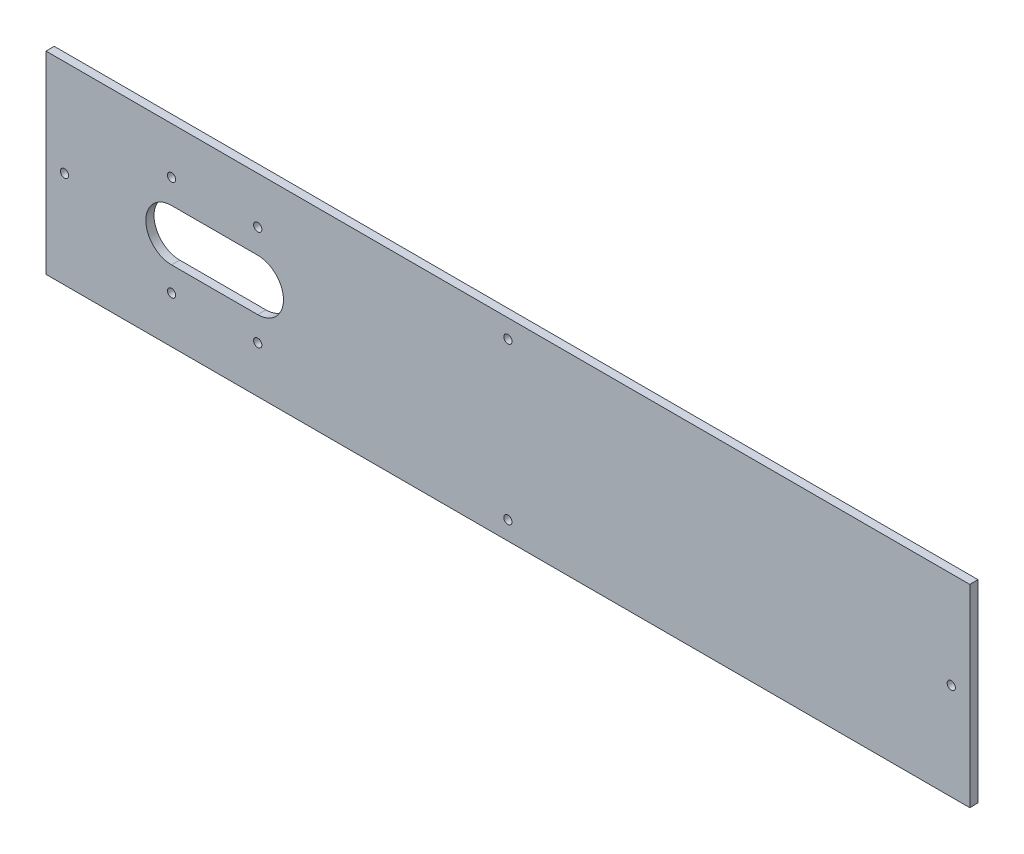
SolidWorks part; units mm, degrees
ref_plane "Piano frontale" through (0, 0, 0) normal (0, 0, 1) x (1, 0, 0)
ref_plane "Piano superiore" through (0, 0, 0) normal (0, 1, 0) x (1, 0, 0)
ref_plane "Piano destro" through (0, 0, 0) normal (1, 0, 0) x (0, 0, -1)
sketch "Schizzo1" plane through (0, 0, 0) normal (0, 0, 1) x (1, 0, 0)
  line L0 (-224.5, 351.6275) -> (-224.5, -66.2585) construction
  line L1 (0, 0) -> (-449, 0)
  line L2 (0, 0) -> (0, 94)
  line L3 (0, 94) -> (-449, 94)
  line L4 (-449, 0) -> (-449, 94)
  line L5 (-387.9788, 47) -> (120.8821, 47) construction
  line L6 (-387.9788, 47) -> (-346.0895, 47) construction
  line L7 (-387.9788, 59.5) -> (-346.0895, 59.5)
  line L8 (-387.9788, 34.5) -> (-346.0895, 34.5)
  line L9 (-367.0341, 47) -> (-367.0341, 59.5) construction
  arc A0 (-387.9788, 59.5) -> (-387.9788, 34.5) centre (-387.9788, 47) ccw
  circle A1 centre (-9, 47) radius 2
  circle A2 centre (-224.5, 85) radius 2
  circle A3 centre (-440, 47) radius 2
  circle A4 centre (-224.5, 9) radius 2
  arc A5 (-346.0895, 34.5) -> (-346.0895, 59.5) centre (-346.0895, 47) ccw
  circle A6 centre (-346.0895, 71.3395) radius 2
  circle A7 centre (-346.0895, 22.6605) radius 2
  circle A8 centre (-387.9788, 22.6605) radius 2
  circle A9 centre (-387.9788, 71.3395) radius 2
  point P9 (-224.5, 47)
  point P10 (-367.0341, 47)
  dimension "D3" = 4
  dimension "D2" = 4
  dimension "D5" = 4
  dimension "D1" = 449
  dimension "314" = 94
  dimension "D4" = 9
  dimension "D6" = 9
  dimension "D7" = 25
extrude "Estrusione-Estrusione1" add sketch "Schizzo1" along normal blind 4
